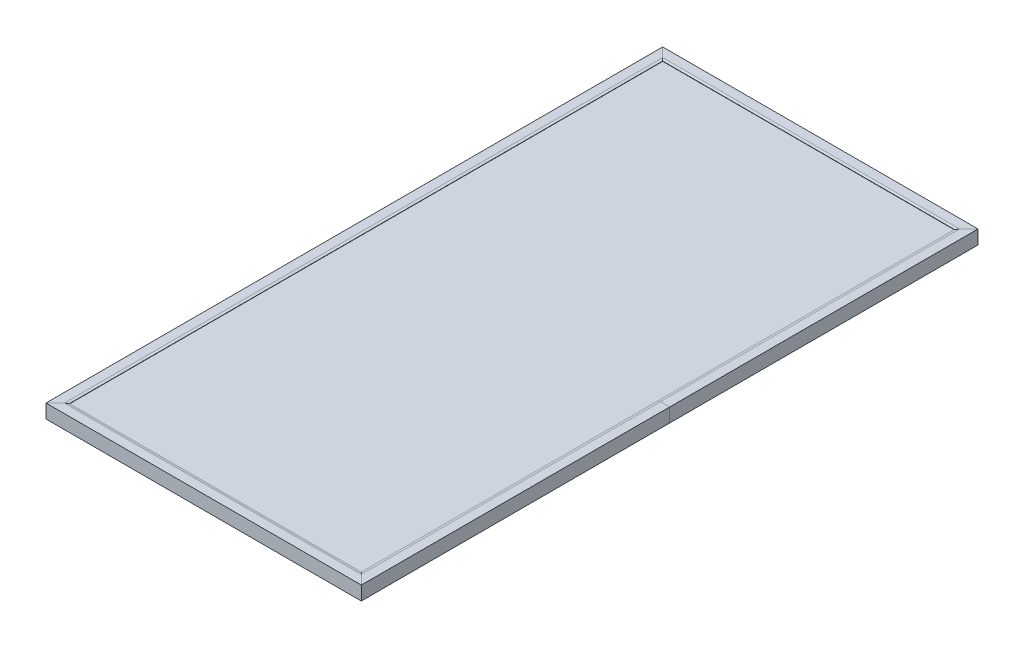
SolidWorks part; units mm, degrees
ref_plane "Front Plane" through (0, 0, 0) normal (0, 0, 1) x (1, 0, 0)
ref_plane "Top Plane" through (0, 0, 0) normal (0, 1, 0) x (1, 0, 0)
ref_plane "Right Plane" through (0, 0, 0) normal (1, 0, 0) x (0, 0, -1)
sketch "Solar Panel Dimensions" plane through (0, 0, 0) normal (0, 1, 0) x (1, 0, 0)
  line L0 (-403.86, 789.94) -> (403.86, 789.94)
  line L1 (-403.86, 789.94) -> (-403.86, -789.94)
  line L2 (403.86, 789.94) -> (403.86, -789.94)
  line L3 (-403.86, -789.94) -> (403.86, -789.94)
  line L4 (-403.86, 789.94) -> (403.86, -789.94) construction
  line L5 (403.86, 789.94) -> (-403.86, -789.94) construction
  point P1 (0, 0)
  dimension "D1" = 1579.88
  dimension "D2" = 807.72
sketch "Bracket" plane through (0, 0, 0) normal (0, 0, 1) x (1, 0, 0)
  line L0 (403.86, 0) -> (373.86, 0)
  line L1 (373.86, 33.56) -> (373.86, 34.2641)
  line L2 (-403.86, 0) -> (403.86, 0) construction
  line L3 (-403.86, 0) -> (403.86, 0) construction
  line L4 (373.86, 0) -> (373.86, 1.2)
  line L5 (373.86, 1.2) -> (399.86, 1.2)
  line L6 (399.86, 1.2) -> (399.86, 33.56)
  line L7 (399.86, 33.56) -> (373.86, 33.56)
  line L8 (373.86, 33.56) -> (373.86, 35.56) construction
  line L9 (373.86, 35.56) -> (403.86, 35.56) construction
  line L10 (403.86, 35.56) -> (403.86, 0)
  line L11 (373.86, 34.2641) -> (380.2941, 35.56)
  line L12 (-403.86, 0) -> (403.86, 0) construction
  line L13 (380.2941, 35.56) -> (403.86, 35.56)
  point P3 (403.86, 0)
  dimension "D1" = 1.2
  dimension "D2" = 2
  dimension "D3" = 4
  dimension "D4" = 35.56
  dimension "D5" = 30
  dimension "D6" = 6.4341
  dimension "D7" = 0.7041
sweep "Sweep1" add profiles "Bracket" path "Solar Panel Dimensions"
sketch "Sketch3" plane through (0, 33.56, 0) normal (0, -1, 0) x (1, 0, 0)
  line L1 (-373.86, 759.94) -> (373.86, 759.94)
  line L2 (-373.86, 759.94) -> (-373.86, -759.94)
  line L3 (-373.86, -759.94) -> (373.86, -759.94)
  line L4 (373.86, 759.94) -> (373.86, -759.94)
extrude "Boss-Extrude1" add sketch "Sketch3" along normal blind 3 separate body
sketch "Sketch4" plane through (0, 30.56, 0) normal (0, -1, 0) x (1, 0, 0)
  line L0 (55, -659.94) -> (-55, -659.94)
  line L1 (-55, -659.94) -> (-55, -584.94)
  line L2 (-55, -584.94) -> (-20, -584.94)
  line L3 (-20, -584.94) -> (-20, -604.94)
  line L4 (-20, -604.94) -> (20, -604.94)
  line L5 (20, -604.94) -> (20, -584.94)
  line L6 (20, -584.94) -> (55, -584.94)
  line L7 (55, -584.94) -> (55, -659.94)
  line L8 (373.86, -759.94) -> (-373.86, -759.94) construction
  line L9 (0, -759.94) -> (0, -659.94) construction
  dimension "D1" = 35
  dimension "D2" = 35
  dimension "D3" = 40
  dimension "D4" = 75
  dimension "D5" = 20
  dimension "D6" = 100
extrude "Boss-Extrude2" add sketch "Sketch4" along normal blind 10
ref_plane "Plane1" through (0, 0, 0) normal (0, -1, 0) x (-1, 0, 0)
sketch "Sketch5" plane through (0, 0, 0) normal (0, -1, 0) x (-1, 0, 0)
  line L0 (-384.36, 651.44) -> (-384.36, 646.44) construction
  line L1 (-379.86, 651.44) -> (-379.86, 646.44)
  line L2 (-388.86, 651.44) -> (-388.86, 646.44)
  line L3 (-403.86, 789.94) -> (-403.86, 0) construction
  line L4 (403.86, 789.94) -> (-403.86, 789.94) construction
  line L5 (-384.36, 401.44) -> (-384.36, 396.44) construction
  line L6 (-379.86, 401.44) -> (-379.86, 396.44)
  line L7 (-388.86, 401.44) -> (-388.86, 396.44)
  line L8 (-384.36, 651.44) -> (-384.36, 609.8863) construction
  line L9 (-384.36, -398.56) -> (-384.36, -403.56) construction
  line L10 (-379.86, -398.56) -> (-379.86, -403.56)
  line L11 (-388.86, -398.56) -> (-388.86, -403.56)
  line L12 (-384.36, -648.56) -> (-384.36, -653.56) construction
  line L13 (-379.86, -648.56) -> (-379.86, -653.56)
  line L14 (-388.86, -648.56) -> (-388.86, -653.56)
  line L15 (-384.36, -398.56) -> (-384.36, 579.3685) construction
  line L16 (0, 881.6947) -> (0, -931.728) construction
  line L17 (384.36, -398.56) -> (384.36, 579.3685) construction
  line L18 (384.36, 651.44) -> (384.36, 609.8863) construction
  line L19 (384.36, -648.56) -> (384.36, -653.56) construction
  line L20 (379.86, -648.56) -> (379.86, -653.56)
  line L21 (388.86, -648.56) -> (388.86, -653.56)
  line L22 (384.36, 401.44) -> (384.36, 396.44) construction
  line L23 (379.86, 401.44) -> (379.86, 396.44)
  line L24 (388.86, 401.44) -> (388.86, 396.44)
  line L25 (384.36, -398.56) -> (384.36, -403.56) construction
  line L26 (379.86, -398.56) -> (379.86, -403.56)
  line L27 (388.86, -398.56) -> (388.86, -403.56)
  line L28 (384.36, 651.44) -> (384.36, 646.44) construction
  line L29 (379.86, 651.44) -> (379.86, 646.44)
  line L30 (388.86, 651.44) -> (388.86, 646.44)
  arc A0 (-379.86, 651.44) -> (-388.86, 651.44) centre (-384.36, 651.44) ccw
  arc A1 (-388.86, 646.44) -> (-379.86, 646.44) centre (-384.36, 646.44) ccw
  arc A2 (-379.86, 401.44) -> (-388.86, 401.44) centre (-384.36, 401.44) ccw
  arc A3 (-388.86, 396.44) -> (-379.86, 396.44) centre (-384.36, 396.44) ccw
  arc A4 (-379.86, -398.56) -> (-388.86, -398.56) centre (-384.36, -398.56) ccw
  arc A5 (-388.86, -403.56) -> (-379.86, -403.56) centre (-384.36, -403.56) ccw
  arc A6 (-379.86, -648.56) -> (-388.86, -648.56) centre (-384.36, -648.56) ccw
  arc A7 (-388.86, -653.56) -> (-379.86, -653.56) centre (-384.36, -653.56) ccw
  arc A8 (379.86, -648.56) -> (388.86, -648.56) centre (384.36, -648.56) cw
  arc A9 (388.86, -653.56) -> (379.86, -653.56) centre (384.36, -653.56) cw
  arc A10 (379.86, 401.44) -> (388.86, 401.44) centre (384.36, 401.44) cw
  arc A11 (388.86, 396.44) -> (379.86, 396.44) centre (384.36, 396.44) cw
  arc A12 (379.86, -398.56) -> (388.86, -398.56) centre (384.36, -398.56) cw
  arc A13 (388.86, -403.56) -> (379.86, -403.56) centre (384.36, -403.56) cw
  arc A14 (379.86, 651.44) -> (388.86, 651.44) centre (384.36, 651.44) cw
  arc A15 (388.86, 646.44) -> (379.86, 646.44) centre (384.36, 646.44) cw
  point P2 (-384.36, 648.94)
  point P10 (-384.36, 641.94)
  point P12 (-384.36, 655.94)
  point P15 (-384.36, -401.06)
  point P18 (-384.36, 398.94)
  point P23 (-384.36, 391.94)
  point P24 (-384.36, 663.1984)
  point P26 (-384.36, 405.94)
  point P27 (-422.1737, 679.0016)
  point P28 (-379.86, 398.94)
  point P34 (-384.36, -408.06)
  point P35 (-384.36, -394.06)
  point P38 (-384.36, -651.06)
  point P43 (-384.36, -658.06)
  point P44 (-732.6396, 632.6806)
  point P45 (-384.36, -644.06)
  point P46 (-379.86, -651.06)
  point P56 (384.36, -644.06)
  point P59 (384.36, -651.06)
  point P64 (384.36, -394.06)
  point P65 (422.1737, 679.0016)
  point P66 (384.36, 405.94)
  point P67 (384.36, 663.1984)
  point P70 (384.36, 398.94)
  point P76 (384.36, -401.06)
  point P81 (384.36, 655.94)
  point P83 (384.36, 648.94)
  dimension "D1" = 15
  dimension "D2" = 9
  dimension "D3" = 14
  dimension "D4" = 134
  dimension "D5" = 9
  dimension "D6" = 14
  dimension "D7" = 250
  dimension "D8" = 14
  dimension "D9" = 9
  dimension "D10" = 14
  dimension "D11" = 250
  dimension "D12" = 9
  dimension "D13" = 800
extrude "Cut-Extrude1" cut sketch "Sketch5" against normal up to next (1.2 mm away)
equation "\"panelthickness\"= 1.4in"
equation "\"D4@Bracket\" = \"panelthickness\""
equation "\"PanelHeight\"=1579.88"
equation "\"D1@Solar Panel Dimensions\"=\"PanelHeight\""
equation "\"PanelWidth\"=807.72"
equation "\"D2@Solar Panel Dimensions\"=\"PanelWidth\""
